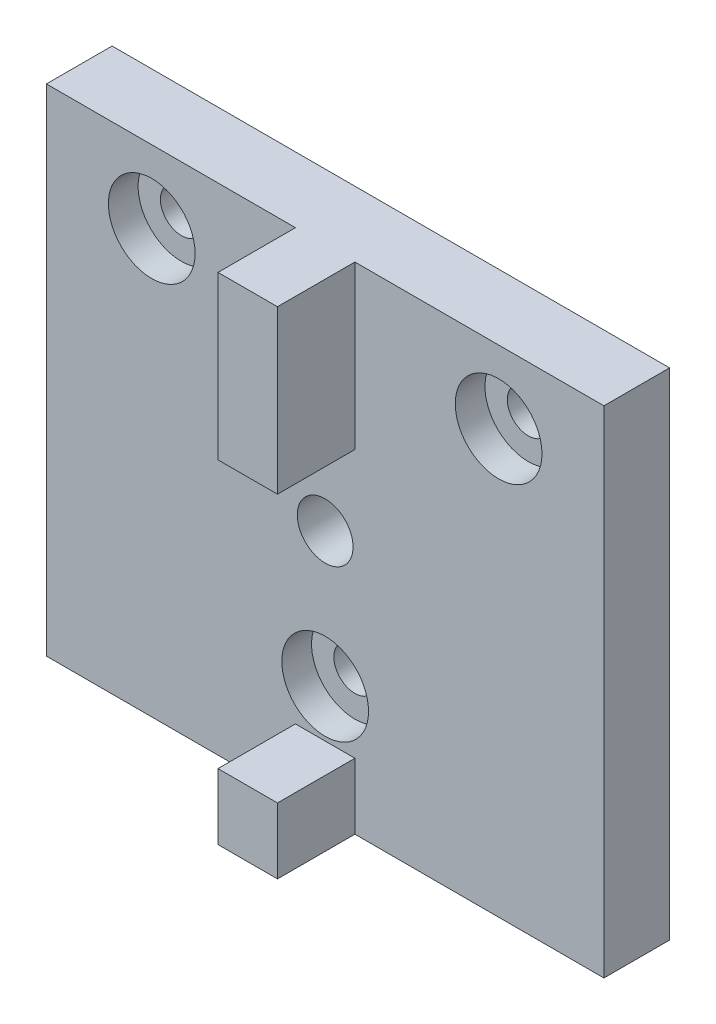
SolidWorks part; units mm, degrees
ref_plane "Plan de face" through (0, 0, 0) normal (0, 0, 1) x (1, 0, 0)
ref_plane "Plan de dessus" through (0, 0, 0) normal (0, 1, 0) x (1, 0, 0)
ref_plane "Plan de droite" through (0, 0, 0) normal (1, 0, 0) x (0, 0, -1)
sketch "Base" plane through (0, 0, 0) normal (0, 1, 0) x (1, 0, 0)
  line L3 (-3, 10.0617) -> (-2.4, 10.0617)
  line L5 (-2.4, 3.8117) -> (2.4, 3.8117)
  line L6 (0, -55) -> (0, 55) construction
  line L7 (2.4, 10.0617) -> (2.4, 3.8117)
  line L8 (3, 10.0617) -> (2.4, 10.0617)
  line L12 (0, 15.3617) -> (0, 3.8117) construction
  line L23 (-22.5, 15.3617) -> (22.5, 15.3617)
  line L32 (-2.4, 10.0617) -> (-2.4, 3.8117)
  line L33 (-22.5, 15.3617) -> (-22.5, 10.0617)
  line L34 (-22.5, 10.0617) -> (-3, 10.0617)
  line L35 (3, 10.0617) -> (22.5, 10.0617)
  line L36 (22.5, 10.0617) -> (22.5, 15.3617)
  point P2 (-15.4, 15.3617)
  point P3 (0, 3.8117)
  point P27 (0, 0)
  dimension "D1" = 6.25
  dimension "D2" = 4.8
  dimension "D3" = 5.3
  dimension "D5" = 45
extrude "Boss.-Extru.1" add sketch "Base" along normal mid plane 40
sketch "Esquisse19" plane through (0, 0, -3.8117) normal (0, 0, 1) x (1, 0, 0)
  line L0 (-2.4, 20) -> (-2.4, -20) construction
  line L1 (-2.4, 6.894) -> (2.4, 6.894)
  line L2 (-2.4, 6.894) -> (-2.4, -14.6873)
  line L3 (-2.4, -14.6873) -> (2.4, -14.6873)
  line L4 (2.4, 6.894) -> (2.4, -14.6873)
  line L5 (2.4, 20) -> (2.4, -20) construction
extrude "Enlèv. mat.-Extru.1" cut sketch "Esquisse19" against normal up to surface (6.25 mm away) up to face at (-12.45, 0, -10.0617)
hole_wizard "Chambrage pour vis à tête ronde bombée M31" positions "Esquisse17" profile "Esquisse18" counterbore size "M3" standard "Ansi Metric" end condition up to next
sketch "Esquisse17" plane through (0, 0, -10.0617) normal (0, 0, 1) x (1, 0, 0)
  line L0 (-14, 14.1423) -> (14, 14.1423) construction
  point P0 (-14, 14.1423)
  point P2 (14, 14.1423)
  point P9 (0, 14.1423)
  point P11 (0, -10.8577)
  dimension "D1" = 28
  dimension "D2" = 25
sketch "Esquisse18" plane through (-14, 14.1423, -10.0617) normal (1, 0, 0) x (0, -1, 0)
  line L0 (0, 0) -> (0, 5.3)
  line L1 (0, 5.3) -> (1.7, 5.3)
  line L3 (1.7, 5.3) -> (1.7, 2.4)
  line L4 (1.7, 2.4) -> (3.5, 2.4)
  line L5 (3.5, 2.4) -> (3.5, 0)
  line L7 (3.5, 0) -> (0, 0)
  line L11 (0, -6.35) -> (0, 107.95) construction
  dimension "Diamètre du perçage jusqu'au prochain" = 3.4
  dimension "Profondeur du perçage jusqu'au prochain" = 5.3
  dimension "Diamètre du chambrage" = 7
  dimension "Profondeur du chambrage" = 2.4
hole_wizard "Dégagement M41" positions "Esquisse20" profile "Esquisse21" hole size "M4" standard "Ansi Metric" end condition up to next
sketch "Esquisse20" plane through (0, 0, -15.3617) normal (0, 0, -1) x (-1, 0, 0)
  point P0 (0, 0)
sketch "Esquisse21" plane through (0, 0, -15.3617) normal (1, 0, 0) x (0, 1, 0)
  line L0 (0, 0) -> (0, 5.3)
  line L1 (0, 5.3) -> (2.25, 5.3)
  line L2 (2.25, 5.3) -> (2.25, 0)
  line L5 (2.25, 0) -> (0, 0)
  line L11 (0, -6.35) -> (0, 107.95) construction
  dimension "Diamètre du perçage jusqu'au prochain" = 4.5
  dimension "Profondeur du perçage jusqu'au prochain" = 5.3
